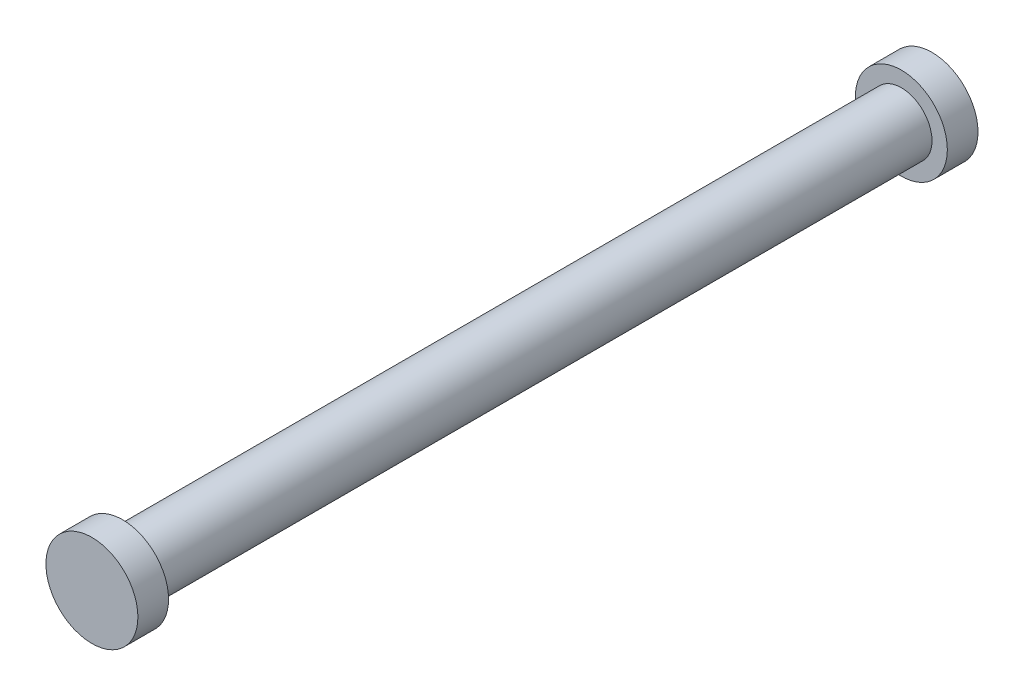
SolidWorks part; units mm, degrees
ref_plane "Front Plane" through (0, 0, 0) normal (0, 0, 1) x (1, 0, 0)
ref_plane "Top Plane" through (0, 0, 0) normal (0, 1, 0) x (1, 0, 0)
ref_plane "Right Plane" through (0, 0, 0) normal (1, 0, 0) x (0, 0, -1)
sketch "Sketch1" plane through (0, 0, 0) normal (0, 0, 1) x (1, 0, 0)
  circle A0 centre (0, 0) radius 5
  circle A1 centre (0, 0) radius 7.5
  dimension "D1" = 10
  dimension "D2" = 15
extrude "Boss-Extrude1" add sketch "Sketch1" along normal blind 137 contours A0 | A1 A0 region at (0, 0, 0) region at (-7.2879, 0, 0)
extrude "Cut-Extrude1" cut sketch "Sketch1<6>" along normal offset from surface (127 mm away) 5 from offset 5 contours A1 A0 region at (-7.2879, 0, 0) up to face at (7.5, 0, 137)
sketch "Sketch1<6>" plane through (0, 0, 0) normal (0, 0, 1) x (1, 0, 0) same geometry as "Sketch1"
